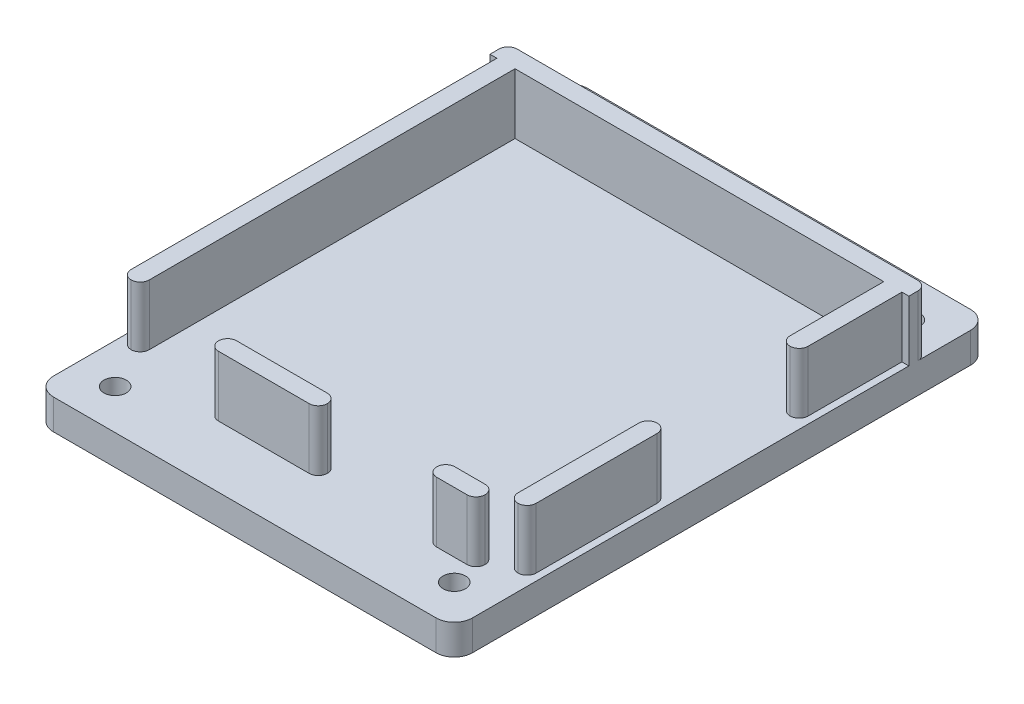
SolidWorks part; units mm, degrees
ref_plane "前视基准面" through (0, 0, 0) normal (0, 0, 1) x (1, 0, 0)
ref_plane "上视基准面" through (0, 0, 0) normal (0, 1, 0) x (1, 0, 0)
ref_plane "右视基准面" through (0, 0, 0) normal (1, 0, 0) x (0, 0, -1)
sketch "草图1" plane through (0, 0, 0) normal (0, 1, 0) x (1, 0, 0)
  line L0 (-34.65, 0) -> (34.65, 0) construction
  line L1 (-34.65, -44.2) -> (34.65, -44.2)
  line L2 (-34.65, 0) -> (34.65, 0) construction
  line L3 (-34.65, -44.2) -> (-34.65, 44.2)
  line L4 (-34.65, 44.2) -> (34.65, 44.2)
  line L5 (34.65, -44.2) -> (34.65, 44.2)
  circle A0 centre (-28.05, 37.6) radius 1.85
  circle A1 centre (28.05, 37.6) radius 1.85
  circle A2 centre (28.05, -37.6) radius 1.85
  circle A3 centre (-28.05, -37.6) radius 1.85
  point P3 (0, 0)
  dimension "D5" = 3.7
  dimension "D1" = 69.3
  dimension "D2" = 44.2
  dimension "D3" = 37.6
  dimension "D4" = 28.05
extrude "凸台-拉伸1" add sketch "草图1" against normal blind 5
sketch "草图3" plane through (0, 0, 0) normal (0, 1, 0) x (1, 0, 0)
  line L0 (-34.65, 44.2) -> (-34.65, -44.2) construction
  line L5 (34.65, -44.2) -> (34.65, 44.2) construction
  line L6 (-34.65, 0) -> (34.65, 0) construction
  line L15 (-34.65, 34) -> (34.65, 34)
  line L20 (34.65, 31) -> (34.65, 34)
  line L21 (-34.65, 31) -> (34.65, 31)
  line L22 (-34.65, 31) -> (-34.65, 34)
  line L23 (20.05, -31) -> (28.05, -31)
  line L24 (28.05, -34) -> (28.05, -31)
  line L25 (20.05, -34) -> (28.05, -34)
  line L26 (20.05, -34) -> (20.05, -31)
  line L27 (-16.05, -31) -> (1.95, -31)
  line L28 (1.95, -34) -> (1.95, -31)
  line L29 (-16.05, -34) -> (1.95, -34)
  line L30 (-16.05, -34) -> (-16.05, -31)
extrude "凸台-拉伸2" add sketch "草图3" along normal blind 10
sketch "草图4" plane through (0, 0, 0) normal (0, 1, 0) x (1, 0, 0)
  line L0 (-34.65, 31) -> (34.65, 31) construction
  line L1 (-30.5, 31) -> (-33.5, 31)
  line L2 (-30.5, 31) -> (-30.5, -31)
  line L3 (-30.5, -31) -> (-33.5, -31)
  line L4 (-33.5, 31) -> (-33.5, -31)
  line L5 (1.95, -31) -> (-16.05, -31) construction
  line L6 (28.05, -31) -> (20.05, -31) construction
  line L7 (30.5, 31) -> (33.5, 31)
  line L8 (30.5, 31) -> (30.5, 14)
  line L9 (30.5, 14) -> (33.5, 14)
  line L10 (33.5, 31) -> (33.5, 14)
  line L11 (30.5, -31) -> (33.5, -31)
  line L12 (30.5, -31) -> (30.5, -8)
  line L13 (30.5, -8) -> (33.5, -8)
  line L14 (33.5, -31) -> (33.5, -8)
  circle A0 centre (-28.05, 37.6) radius 1.85 construction
  circle A2 centre (28.05, 37.6) radius 1.85 construction
  point P6 (-29.9, 37.6)
  point P19 (29.9, 37.6)
  dimension "D1" = 0.6
  dimension "D2" = 3
  dimension "D3" = 0.6
  dimension "D4" = 3
  dimension "D5" = 17
  dimension "D6" = 23
extrude "凸台-拉伸3" add sketch "草图4" along normal blind 10
fillet "圆角1" radius 3 4 edges at (-34.65, -2.5, -44.2) (34.65, -2.5, -44.2) (34.65, -2.5, 44.2) (-34.65, -2.5, 44.2)
fillet "圆角2" radius 1.5 8 edges at (20.05, 5, 34) (20.05, 5, 31) (28.05, 5, 31) (28.05, 5, 34) (-16.05, 5, 34) (-16.05, 5, 31) (1.95, 5, 34) (1.95, 5, 31)
fillet "圆角3" radius 1.5 10 edges at (34.65, 5, -34) (-34.65, 5, -34) (-30.5, 5, 31) (-33.5, 5, 31) (33.5, 5, 31) (30.5, 5, 31) (33.5, 5, 8) (30.5, 5, 8) (33.5, 5, -14) (30.5, 5, -14)
